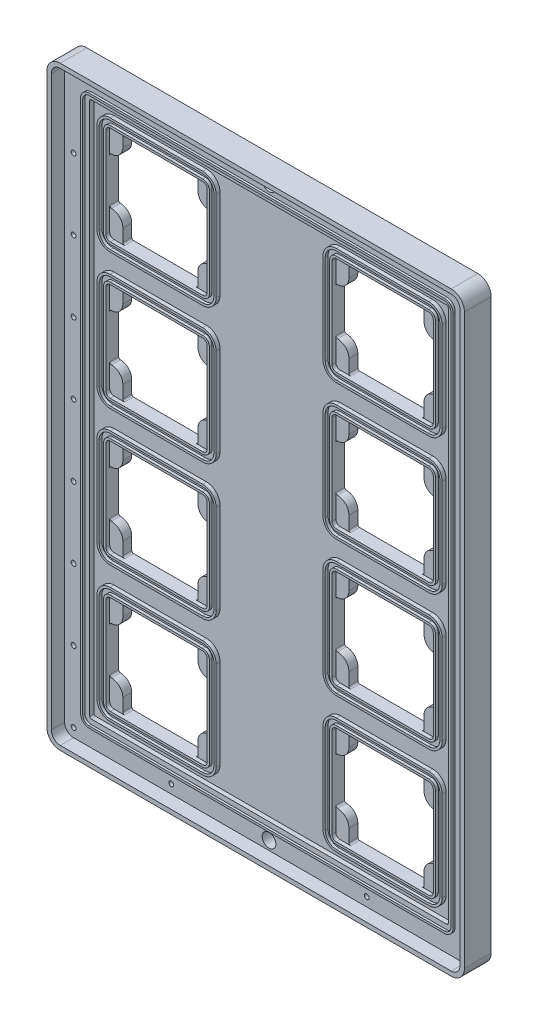
SolidWorks part; units mm, degrees
ref_plane "Front Plane" through (0, 0, 0) normal (0, 0, 1) x (1, 0, 0)
ref_plane "Top Plane" through (0, 0, 0) normal (0, 1, 0) x (1, 0, 0)
ref_plane "Right Plane" through (0, 0, 0) normal (1, 0, 0) x (0, 0, -1)
sketch "Sketch1" plane through (0, 0, 0) normal (0, 0, 1) x (1, 0, 0)
  line L1 (0, 0) -> (292.1, 0)
  line L2 (0, 0) -> (0, 419.1)
  line L3 (0, 419.1) -> (292.1, 419.1)
  line L4 (292.1, 0) -> (292.1, 419.1)
  dimension "D1" = 419.1
  dimension "D2" = 292.1
extrude "Boss-Extrude1" add sketch "Sketch1" along normal blind 9.525
sketch "Sketch4" plane through (0, 0, 9.525) normal (0, 0, 1) x (1, 0, 0)
  line L3 (0, 419.1) -> (0, 0) construction
  line L4 (6.35, 412.75) -> (285.75, 412.75) construction
  line L5 (6.35, 412.75) -> (6.35, 6.35) construction
  line L6 (6.35, 6.35) -> (285.75, 6.35) construction
  line L7 (285.75, 412.75) -> (285.75, 6.35) construction
  line L8 (292.1, 419.1) -> (0, 419.1) construction
  line L9 (292.1, 0) -> (292.1, 419.1) construction
  line L10 (0, 0) -> (292.1, 0) construction
  circle A0 centre (6.35, 6.35) radius 1.7272
  circle A1 centre (6.35, 412.75) radius 1.7272
  circle A2 centre (285.75, 412.75) radius 1.7272
  circle A3 centre (285.75, 6.35) radius 1.7272
  dimension "D5" = 3.4544
  dimension "D1" = 6.35
  dimension "D2" = 6.35
  dimension "D3" = 6.35
  dimension "D4" = 6.35
extrude "Cut-Extrude1" cut sketch "Sketch4" against normal blind 6.985
pattern_linear "LPattern2" count 8 spacing 50.8 along (0, -1, 0) of "Cut-Extrude1"
pattern_linear "LPattern3" count 4 spacing 69.85 along (-1, 0, 0) of "Cut-Extrude1"
sketch "Sketch5" plane through (0, 0, 9.525) normal (0, 0, 1) x (1, 0, 0)
  line L0 (0, 419.1) -> (0, 0) construction
  line L1 (19.05, 406.4) -> (273.05, 406.4) construction
  line L2 (12.7, 400.05) -> (12.7, 19.05) construction
  line L3 (19.05, 12.7) -> (273.05, 12.7) construction
  line L4 (279.4, 400.05) -> (279.4, 19.05) construction
  line L5 (292.1, 419.1) -> (0, 419.1) construction
  line L6 (292.1, 0) -> (292.1, 419.1) construction
  line L7 (0, 0) -> (292.1, 0) construction
  line L8 (19.05, 14.732) -> (273.05, 14.732) construction
  line L9 (14.732, 400.05) -> (14.732, 19.05) construction
  line L10 (19.05, 404.368) -> (273.05, 404.368) construction
  line L11 (277.368, 400.05) -> (277.368, 19.05) construction
  line L12 (12.954, 400.05) -> (12.954, 19.05)
  line L13 (19.05, 406.146) -> (273.05, 406.146)
  line L14 (279.146, 400.05) -> (279.146, 19.05)
  line L15 (19.05, 12.954) -> (273.05, 12.954)
  line L16 (277.622, 400.05) -> (277.622, 19.05)
  line L17 (19.05, 404.622) -> (273.05, 404.622)
  line L18 (14.478, 400.05) -> (14.478, 19.05)
  line L19 (19.05, 14.478) -> (273.05, 14.478)
  arc A0 (273.05, 12.7) -> (279.4, 19.05) centre (273.05, 19.05) ccw construction
  arc A1 (12.7, 19.05) -> (19.05, 12.7) centre (19.05, 19.05) ccw construction
  arc A2 (273.05, 406.4) -> (279.4, 400.05) centre (273.05, 400.05) cw construction
  arc A3 (19.05, 406.4) -> (12.7, 400.05) centre (19.05, 400.05) ccw construction
  arc A4 (14.732, 19.05) -> (19.05, 14.732) centre (19.05, 19.05) ccw construction
  arc A5 (19.05, 404.368) -> (14.732, 400.05) centre (19.05, 400.05) ccw construction
  arc A6 (273.05, 404.368) -> (277.368, 400.05) centre (273.05, 400.05) cw construction
  arc A7 (273.05, 14.732) -> (277.368, 19.05) centre (273.05, 19.05) ccw construction
  arc A8 (19.05, 406.146) -> (12.954, 400.05) centre (19.05, 400.05) ccw
  arc A9 (273.05, 406.146) -> (279.146, 400.05) centre (273.05, 400.05) cw
  arc A10 (273.05, 12.954) -> (279.146, 19.05) centre (273.05, 19.05) ccw
  arc A11 (12.954, 19.05) -> (19.05, 12.954) centre (19.05, 19.05) ccw
  arc A12 (273.05, 404.622) -> (277.622, 400.05) centre (273.05, 400.05) cw
  arc A13 (19.05, 404.622) -> (14.478, 400.05) centre (19.05, 400.05) ccw
  arc A14 (14.478, 19.05) -> (19.05, 14.478) centre (19.05, 19.05) ccw
  arc A15 (273.05, 14.478) -> (277.622, 19.05) centre (273.05, 19.05) ccw
  dimension "D5" = 6.35
  dimension "D1" = 12.7
  dimension "D2" = 12.7
  dimension "D3" = 12.7
  dimension "D4" = 12.7
  dimension "D6" = 2.032
  dimension "D7" = 2.032
  dimension "D8" = 0.254
  dimension "D9" = 0.254
  dimension "D10" = 0.254
sketch "Sketch6" plane through (0, 0, 9.525) normal (0, 0, 1) x (1, 0, 0)
  line L24 (273.05, 401.193) -> (19.05, 401.193)
  line L25 (274.193, 19.05) -> (274.193, 400.05)
  line L26 (19.05, 17.907) -> (273.05, 17.907)
  line L27 (17.907, 400.05) -> (17.907, 19.05)
  line L28 (273.05, 401.193) -> (19.05, 401.193)
  line L29 (274.193, 19.05) -> (274.193, 400.05)
  line L30 (19.05, 17.907) -> (273.05, 17.907)
  line L31 (17.907, 400.05) -> (17.907, 19.05)
  arc A20 (19.05, 401.193) -> (17.907, 400.05) centre (19.05, 400.05) ccw
  arc A21 (274.193, 400.05) -> (273.05, 401.193) centre (273.05, 400.05) ccw
  arc A22 (273.05, 17.907) -> (274.193, 19.05) centre (273.05, 19.05) ccw
  arc A23 (17.907, 19.05) -> (19.05, 17.907) centre (19.05, 19.05) ccw
  arc A24 (19.05, 401.193) -> (17.907, 400.05) centre (19.05, 400.05) ccw
  arc A25 (274.193, 400.05) -> (273.05, 401.193) centre (273.05, 400.05) ccw
  arc A26 (273.05, 17.907) -> (274.193, 19.05) centre (273.05, 19.05) ccw
  arc A27 (17.907, 19.05) -> (19.05, 17.907) centre (19.05, 19.05) ccw
  dimension "D1" = 3.175
extrude "Cut-Extrude3" cut sketch "Sketch6" against normal blind 3.175
extrude "Boss-Extrude2" add sketch "Sketch5" along normal blind 1.5875 contours L12 A11 L15 A10 L14 A9 L13 A8 A15 L19 A14 L18 A13 L17 A12 L16 region at (15.0752, 404.0248, 9.525)
sketch "Sketch7" plane through (0, 0, 9.525) normal (0, 0, 1) x (1, 0, 0)
  circle A0 centre (146.05, 6.35) radius 4.9022
  circle A1 centre (146.05, 412.75) radius 4.9022
  dimension "D1" = 9.8044
extrude "Cut-Extrude4" cut sketch "Sketch7" against normal through all
fillet "Fillet1" radius 6.35 4 edges at (0, 419.1, 4.7625) (292.1, 419.1, 4.7625) (0, 0, 4.7625) (292.1, 0, 4.7625)
sketch "Sketch8" plane through (0, 0, 0) normal (0, 0, -1) x (-1, 0, 0)
  line L0 (-264.668, 370.459) -> (-264.668, 339.2678)
  line L1 (-255.27, 329.8698) -> (-255.27, 320.8782)
  line L2 (-252.4506, 318.0588) -> (-201.2442, 318.0588)
  line L3 (-198.4248, 320.8782) -> (-198.4248, 329.8698)
  line L4 (-189.0268, 339.2678) -> (-189.0268, 370.459)
  line L5 (-198.4248, 379.857) -> (-198.4248, 388.8486)
  line L6 (-201.2442, 391.668) -> (-252.4506, 391.668)
  line L7 (-255.27, 388.8486) -> (-255.27, 379.857)
  line L8 (-261.8486, 391.668) -> (-261.8486, 318.0588) construction
  line L9 (-264.668, 388.8486) -> (-189.0268, 388.8486) construction
  line L10 (-264.668, 391.668) -> (-189.0268, 391.668) construction
  line L11 (-264.668, 391.668) -> (-264.668, 318.0588) construction
  line L12 (-264.668, 318.0588) -> (-189.0268, 318.0588) construction
  line L13 (-189.0268, 391.668) -> (-189.0268, 318.0588) construction
  line L14 (-264.668, 379.857) -> (-189.0268, 379.857) construction
  line L15 (-264.668, 370.459) -> (-189.0268, 370.459) construction
  line L16 (-264.668, 339.2678) -> (-189.0268, 339.2678) construction
  line L17 (-264.668, 329.8698) -> (-189.0268, 329.8698) construction
  line L18 (-264.668, 320.8782) -> (-189.0268, 320.8782) construction
  line L19 (-255.27, 318.0588) -> (-255.27, 391.668) construction
  line L20 (-252.4506, 391.668) -> (-252.4506, 318.0588) construction
  line L21 (-201.2442, 391.668) -> (-201.2442, 318.0588) construction
  line L22 (-198.4248, 391.668) -> (-198.4248, 318.0588) construction
  line L23 (-191.8462, 318.0588) -> (-191.8462, 391.668) construction
  line L24 (-189.0268, 373.2784) -> (-264.668, 373.2784) construction
  line L27 (-201.2442, 393.7) -> (-252.4506, 393.7)
  line L28 (-257.302, 388.8486) -> (-257.302, 379.857)
  line L29 (-266.7, 370.459) -> (-266.7, 339.2678)
  line L30 (-257.302, 329.8698) -> (-257.302, 320.8782)
  line L31 (-252.4506, 316.0268) -> (-201.2442, 316.0268)
  line L32 (-196.3928, 320.8782) -> (-196.3928, 329.8698)
  line L33 (-186.9948, 339.2678) -> (-186.9948, 370.459)
  line L34 (-196.3928, 379.857) -> (-196.3928, 388.8486)
  line L35 (-285.75, 419.1) -> (-6.35, 419.1) construction
  line L36 (-292.1, 6.35) -> (-292.1, 412.75) construction
  arc A0 (-261.8486, 373.2784) -> (-255.27, 379.857) centre (-261.8486, 379.857) ccw
  arc A1 (-261.8486, 373.2784) -> (-264.668, 370.459) centre (-261.8486, 370.459) ccw
  arc A2 (-264.668, 339.2678) -> (-261.8486, 336.4484) centre (-261.8486, 339.2678) ccw
  arc A3 (-255.27, 329.8698) -> (-261.8486, 336.4484) centre (-261.8486, 329.8698) ccw
  arc A4 (-255.27, 320.8782) -> (-252.4506, 318.0588) centre (-252.4506, 320.8782) ccw
  arc A5 (-201.2442, 318.0588) -> (-198.4248, 320.8782) centre (-201.2442, 320.8782) ccw
  arc A6 (-191.8462, 336.4484) -> (-198.4248, 329.8698) centre (-191.8462, 329.8698) ccw
  arc A7 (-191.8462, 336.4484) -> (-189.0268, 339.2678) centre (-191.8462, 339.2678) ccw
  arc A8 (-189.0268, 370.459) -> (-191.8462, 373.2784) centre (-191.8462, 370.459) ccw
  arc A9 (-198.4248, 379.857) -> (-191.8462, 373.2784) centre (-191.8462, 379.857) ccw
  arc A10 (-198.4248, 388.8486) -> (-201.2442, 391.668) centre (-201.2442, 388.8486) ccw
  arc A11 (-252.4506, 391.668) -> (-255.27, 388.8486) centre (-252.4506, 388.8486) ccw
  arc A12 (-252.4506, 393.7) -> (-257.302, 388.8486) centre (-252.4506, 388.8486) ccw
  arc A13 (-261.8486, 375.3104) -> (-257.302, 379.857) centre (-261.8486, 379.857) ccw
  arc A14 (-261.8486, 375.3104) -> (-266.7, 370.459) centre (-261.8486, 370.459) ccw
  arc A15 (-266.7, 339.2678) -> (-261.8486, 334.4164) centre (-261.8486, 339.2678) ccw
  arc A16 (-257.302, 329.8698) -> (-261.8486, 334.4164) centre (-261.8486, 329.8698) ccw
  arc A17 (-257.302, 320.8782) -> (-252.4506, 316.0268) centre (-252.4506, 320.8782) ccw
  arc A18 (-201.2442, 316.0268) -> (-196.3928, 320.8782) centre (-201.2442, 320.8782) ccw
  arc A19 (-191.8462, 334.4164) -> (-196.3928, 329.8698) centre (-191.8462, 329.8698) ccw
  arc A20 (-191.8462, 334.4164) -> (-186.9948, 339.2678) centre (-191.8462, 339.2678) ccw
  arc A21 (-186.9948, 370.459) -> (-191.8462, 375.3104) centre (-191.8462, 370.459) ccw
  arc A22 (-196.3928, 379.857) -> (-191.8462, 375.3104) centre (-191.8462, 379.857) ccw
  arc A23 (-196.3928, 388.8486) -> (-201.2442, 393.7) centre (-201.2442, 388.8486) ccw
  dimension "D4" = 11.811
  dimension "D5" = 21.209
  dimension "D6" = 52.4002
  dimension "D1" = 73.6092
  dimension "D2" = 75.6412
  dimension "D3" = 2.8194
  dimension "D7" = 61.7982
  dimension "D8" = 70.7898
  dimension "D9" = 2.8194
  dimension "D10" = 9.398
  dimension "D11" = 12.2174
  dimension "D12" = 63.4238
  dimension "D13" = 66.2432
  dimension "D14" = 72.8218
  dimension "D15" = 55.2196
  dimension "D16" = 25.4
  dimension "D17" = 25.4
  dimension "D18" = 2.032
extrude "Cut-Extrude5" cut sketch "Sketch8" against normal blind 3.175
sketch "Sketch10" plane through (0, 0, 0) normal (0, 0, -1) x (-1, 0, 0)
  line L18 (-263.0805, 370.459) -> (-263.0805, 339.2678)
  line L19 (-253.6825, 329.8698) -> (-253.6825, 320.8782)
  line L20 (-252.4506, 319.6463) -> (-201.2442, 319.6463)
  line L21 (-200.0123, 320.8782) -> (-200.0123, 329.8698)
  line L22 (-190.6143, 339.2678) -> (-190.6143, 370.459)
  line L23 (-200.0123, 379.857) -> (-200.0123, 388.8486)
  line L24 (-201.2442, 390.0805) -> (-252.4506, 390.0805)
  line L25 (-253.6825, 388.8486) -> (-253.6825, 379.857)
  line L26 (-263.0805, 370.459) -> (-263.0805, 339.2678)
  line L27 (-253.6825, 329.8698) -> (-253.6825, 320.8782)
  line L28 (-252.4506, 319.6463) -> (-201.2442, 319.6463)
  line L29 (-200.0123, 320.8782) -> (-200.0123, 329.8698)
  line L30 (-190.6143, 339.2678) -> (-190.6143, 370.459)
  line L31 (-200.0123, 379.857) -> (-200.0123, 388.8486)
  line L32 (-201.2442, 390.0805) -> (-252.4506, 390.0805)
  line L33 (-253.6825, 388.8486) -> (-253.6825, 379.857)
  arc A28 (-261.8486, 371.6909) -> (-263.0805, 370.459) centre (-261.8486, 370.459) ccw
  arc A29 (-263.0805, 339.2678) -> (-261.8486, 338.0359) centre (-261.8486, 339.2678) ccw
  arc A30 (-253.6825, 329.8698) -> (-261.8486, 338.0359) centre (-261.8486, 329.8698) ccw
  arc A31 (-253.6825, 320.8782) -> (-252.4506, 319.6463) centre (-252.4506, 320.8782) ccw
  arc A32 (-201.2442, 319.6463) -> (-200.0123, 320.8782) centre (-201.2442, 320.8782) ccw
  arc A33 (-191.8462, 338.0359) -> (-200.0123, 329.8698) centre (-191.8462, 329.8698) ccw
  arc A34 (-191.8462, 338.0359) -> (-190.6143, 339.2678) centre (-191.8462, 339.2678) ccw
  arc A35 (-190.6143, 370.459) -> (-191.8462, 371.6909) centre (-191.8462, 370.459) ccw
  arc A36 (-200.0123, 379.857) -> (-191.8462, 371.6909) centre (-191.8462, 379.857) ccw
  arc A37 (-200.0123, 388.8486) -> (-201.2442, 390.0805) centre (-201.2442, 388.8486) ccw
  arc A38 (-252.4506, 390.0805) -> (-253.6825, 388.8486) centre (-252.4506, 388.8486) ccw
  arc A39 (-261.8486, 371.6909) -> (-253.6825, 379.857) centre (-261.8486, 379.857) ccw
  arc A40 (-261.8486, 371.6909) -> (-263.0805, 370.459) centre (-261.8486, 370.459) ccw
  arc A41 (-263.0805, 339.2678) -> (-261.8486, 338.0359) centre (-261.8486, 339.2678) ccw
  arc A42 (-253.6825, 329.8698) -> (-261.8486, 338.0359) centre (-261.8486, 329.8698) ccw
  arc A43 (-253.6825, 320.8782) -> (-252.4506, 319.6463) centre (-252.4506, 320.8782) ccw
  arc A44 (-201.2442, 319.6463) -> (-200.0123, 320.8782) centre (-201.2442, 320.8782) ccw
  arc A45 (-191.8462, 338.0359) -> (-200.0123, 329.8698) centre (-191.8462, 329.8698) ccw
  arc A46 (-191.8462, 338.0359) -> (-190.6143, 339.2678) centre (-191.8462, 339.2678) ccw
  arc A47 (-190.6143, 370.459) -> (-191.8462, 371.6909) centre (-191.8462, 370.459) ccw
  arc A48 (-200.0123, 379.857) -> (-191.8462, 371.6909) centre (-191.8462, 379.857) ccw
  arc A49 (-200.0123, 388.8486) -> (-201.2442, 390.0805) centre (-201.2442, 388.8486) ccw
  arc A50 (-252.4506, 390.0805) -> (-253.6825, 388.8486) centre (-252.4506, 388.8486) ccw
  arc A51 (-261.8486, 371.6909) -> (-253.6825, 379.857) centre (-261.8486, 379.857) ccw
  dimension "D1" = 1.5875
extrude "Cut-Extrude6" cut sketch "Sketch10" against normal through all
sketch "Sketch11" plane through (0, 0, 0) normal (0, 0, -1) x (-1, 0, 0)
  line L0 (-226.8474, 388.8994) -> (-226.8474, 393.7) construction
  line L1 (-261.8486, 388.8994) -> (-191.8462, 388.8994) construction
  line L2 (-261.8486, 388.8994) -> (-261.8486, 320.8274) construction
  line L3 (-261.8486, 320.8274) -> (-191.8462, 320.8274) construction
  line L4 (-191.8462, 388.8994) -> (-191.8462, 320.8274) construction
  line L5 (-201.2442, 393.7) -> (-252.4506, 393.7) construction
  line L6 (-226.8474, 320.8274) -> (-226.8474, 316.0268) construction
  line L7 (-252.4506, 316.0268) -> (-201.2442, 316.0268) construction
  line L8 (-261.8486, 354.8634) -> (-266.7, 354.8634) construction
  line L9 (-266.7, 370.459) -> (-266.7, 339.2678) construction
  line L10 (-191.8462, 354.8634) -> (-186.9948, 354.8634) construction
  line L11 (-186.9948, 339.2678) -> (-186.9948, 370.459) construction
  circle A0 centre (-261.8486, 388.8994) radius 1.1303
  circle A1 centre (-191.8462, 388.8994) radius 1.1303
  circle A2 centre (-191.8462, 320.8274) radius 1.1303
  circle A3 centre (-261.8486, 320.8274) radius 1.1303
  dimension "D3" = 2.2606
  dimension "D1" = 70.0024
  dimension "D2" = 68.072
extrude "Cut-Extrude7" cut sketch "Sketch11" against normal blind 3.9688
sketch "Sketch12" plane through (0, 0, 6.35) normal (0, 0, 1) x (1, 0, 0)
  line L0 (252.4506, 390.0805) -> (201.2442, 390.0805) construction
  line L1 (193.7893, 390.0805) -> (259.9055, 390.0805)
  line L2 (190.6143, 386.9055) -> (190.6143, 322.8213)
  line L3 (193.7893, 319.6463) -> (259.9055, 319.6463)
  line L4 (263.0805, 386.9055) -> (263.0805, 322.8213)
  line L5 (263.0805, 339.2678) -> (263.0805, 370.459) construction
  line L10 (193.7893, 391.668) -> (259.9055, 391.668)
  line L11 (264.668, 386.9055) -> (264.668, 322.8213)
  line L12 (193.7893, 318.0588) -> (259.9055, 318.0588)
  line L13 (189.0268, 386.9055) -> (189.0268, 322.8213)
  line L14 (185.8518, 386.9055) -> (185.8518, 322.8213)
  line L15 (193.7893, 314.8838) -> (259.9055, 314.8838)
  line L16 (267.843, 386.9055) -> (267.843, 322.8213)
  line L17 (193.7893, 394.843) -> (259.9055, 394.843)
  line L18 (184.2643, 386.9055) -> (184.2643, 322.8213)
  line L19 (193.7893, 313.2963) -> (259.9055, 313.2963)
  line L20 (269.4305, 386.9055) -> (269.4305, 322.8213)
  line L21 (193.7893, 396.4305) -> (259.9055, 396.4305)
  line L22 (201.2442, 319.6463) -> (252.4506, 319.6463) construction
  line L23 (190.6143, 370.459) -> (190.6143, 339.2678) construction
  arc A0 (259.9055, 319.6463) -> (263.0805, 322.8213) centre (259.9055, 322.8213) ccw
  arc A1 (190.6143, 322.8213) -> (193.7893, 319.6463) centre (193.7893, 322.8213) ccw
  arc A2 (259.9055, 390.0805) -> (263.0805, 386.9055) centre (259.9055, 386.9055) cw
  arc A3 (193.7893, 390.0805) -> (190.6143, 386.9055) centre (193.7893, 386.9055) ccw
  arc A4 (259.9055, 391.668) -> (264.668, 386.9055) centre (259.9055, 386.9055) cw
  arc A5 (259.9055, 318.0588) -> (264.668, 322.8213) centre (259.9055, 322.8213) ccw
  arc A6 (189.0268, 322.8213) -> (193.7893, 318.0588) centre (193.7893, 322.8213) ccw
  arc A7 (193.7893, 391.668) -> (189.0268, 386.9055) centre (193.7893, 386.9055) ccw
  arc A8 (185.8518, 322.8213) -> (193.7893, 314.8838) centre (193.7893, 322.8213) ccw
  arc A9 (259.9055, 314.8838) -> (267.843, 322.8213) centre (259.9055, 322.8213) ccw
  arc A10 (259.9055, 394.843) -> (267.843, 386.9055) centre (259.9055, 386.9055) cw
  arc A11 (193.7893, 394.843) -> (185.8518, 386.9055) centre (193.7893, 386.9055) ccw
  arc A12 (184.2643, 322.8213) -> (193.7893, 313.2963) centre (193.7893, 322.8213) ccw
  arc A13 (259.9055, 313.2963) -> (269.4305, 322.8213) centre (259.9055, 322.8213) ccw
  arc A14 (259.9055, 396.4305) -> (269.4305, 386.9055) centre (259.9055, 386.9055) cw
  arc A15 (193.7893, 396.4305) -> (184.2643, 386.9055) centre (193.7893, 386.9055) ccw
  dimension "D1" = 3.175
  dimension "D2" = 1.5875
  dimension "D3" = 3.175
  dimension "D4" = 1.5875
extrude "Boss-Extrude3" add sketch "Sketch12" along normal blind 2.794 contours L21 A15 L18 A12 L19 A13 L20 A14 A11 L17 A10 L16 A9 L15 A8 L14 | L10 A7 L13 A6 L12 A5 L11 A4 A3 L1 A2 L4 A0 L3 A1 L2 region at (226.8474, 390.6125, 6.35) region at (187.8957, 392.7991, 6.35)
extrude "Boss-Extrude4" add sketch "Sketch12<3>" along normal blind 0.7937 contours L17 A11 L14 A8 L15 A9 L16 A10 A7 L10 A4 L11 A5 L12 A6 L13 region at (188.9865, 391.7083, 6.35)
sketch "Sketch12<3>" plane through (0, 0, 6.35) normal (0, 0, 1) x (1, 0, 0) same geometry as "Sketch12"
pattern_linear "LPattern1" count 2 spacing 161.5948 along (-1, 0, 0) count 4 spacing 96.8756 along (0, -1, 0) of "Cut-Extrude6", "Cut-Extrude5", "Cut-Extrude7", "Boss-Extrude3", "Boss-Extrude4"
sketch "Sketch13" plane through (0, 0, 0) normal (0, 0, -1) x (-1, 0, 0)
  line L4 (-6.35, 419.1) -> (-285.75, 419.1)
  line L5 (-292.1, 412.75) -> (-292.1, 6.35)
  line L6 (-285.75, 0) -> (-6.35, 0)
  line L7 (0, 6.35) -> (0, 412.75)
  line L8 (-285.75, -3.175) -> (-6.35, -3.175)
  line L9 (3.175, 6.35) -> (3.175, 412.75)
  line L10 (-6.35, 422.275) -> (-285.75, 422.275)
  line L11 (-295.275, 412.75) -> (-295.275, 6.35)
  line L12 (-285.75, -3.175) -> (-6.35, -3.175)
  line L13 (3.175, 6.35) -> (3.175, 412.75)
  line L14 (-6.35, 422.275) -> (-285.75, 422.275)
  line L15 (-295.275, 412.75) -> (-295.275, 6.35)
  arc A4 (-285.75, 419.1) -> (-292.1, 412.75) centre (-285.75, 412.75) ccw
  arc A5 (-292.1, 6.35) -> (-285.75, 0) centre (-285.75, 6.35) ccw
  arc A6 (-6.35, 0) -> (0, 6.35) centre (-6.35, 6.35) ccw
  arc A7 (0, 412.75) -> (-6.35, 419.1) centre (-6.35, 412.75) ccw
  arc A8 (-295.275, 6.35) -> (-285.75, -3.175) centre (-285.75, 6.35) ccw
  arc A9 (-6.35, -3.175) -> (3.175, 6.35) centre (-6.35, 6.35) ccw
  arc A10 (3.175, 412.75) -> (-6.35, 422.275) centre (-6.35, 412.75) ccw
  arc A11 (-285.75, 422.275) -> (-295.275, 412.75) centre (-285.75, 412.75) ccw
  arc A12 (-295.275, 6.35) -> (-285.75, -3.175) centre (-285.75, 6.35) ccw
  arc A13 (-6.35, -3.175) -> (3.175, 6.35) centre (-6.35, 6.35) ccw
  arc A14 (3.175, 412.75) -> (-6.35, 422.275) centre (-6.35, 412.75) ccw
  arc A15 (-285.75, 422.275) -> (-295.275, 412.75) centre (-285.75, 412.75) ccw
  dimension "D1" = 3.175
  dimension "D2" = 3.175
extrude "Boss-Extrude5" add sketch "Sketch13" against normal blind 19.05
